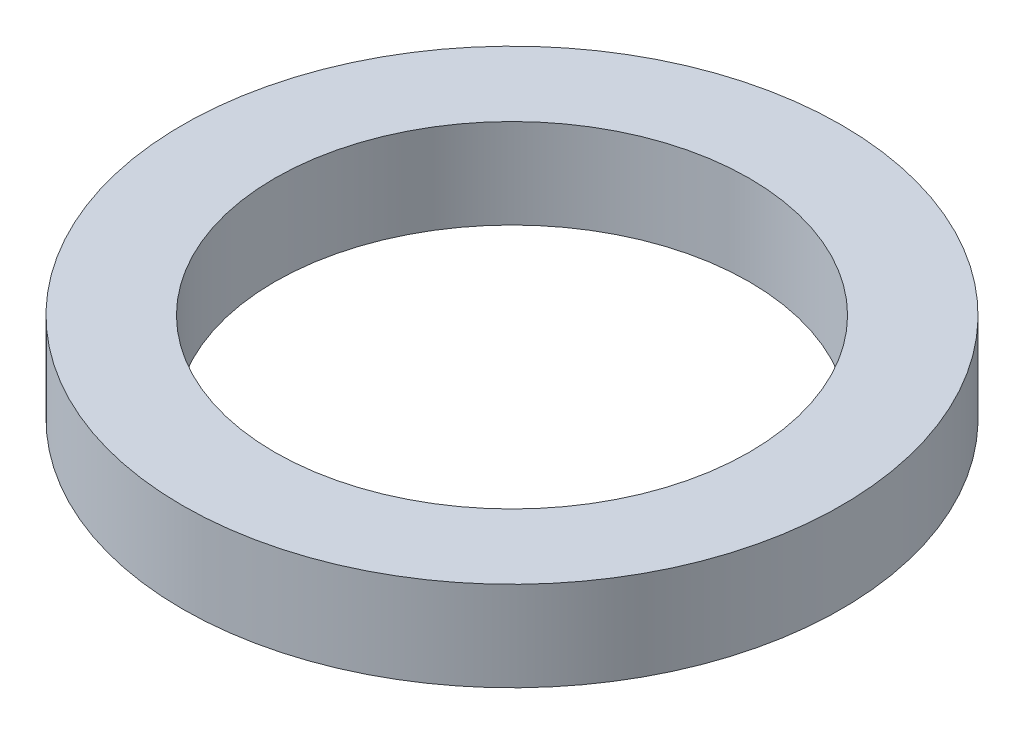
SolidWorks part; units mm, degrees
ref_plane "Front Plane" through (0, 0, 0) normal (0, 0, 1) x (1, 0, 0)
ref_plane "Top Plane" through (0, 0, 0) normal (0, 1, 0) x (1, 0, 0)
ref_plane "Right Plane" through (0, 0, 0) normal (1, 0, 0) x (0, 0, -1)
sketch "Sketch1" plane through (0, 0, 0) normal (0, 1, 0) x (1, 0, 0)
  circle A0 centre (0, 0) radius 62.5
  dimension "FLANGE_OD" = 125
extrude "Boss-Extrude1" add sketch "Sketch1" along normal blind 17
sketch "Sketch2" plane through (0, 0, 0) normal (0, 1, 0) x (1, 0, 0)
  circle A0 centre (0, 0) radius 45
  dimension "BORE_D" = 90
extrude "Cut-Extrude1" cut sketch "Sketch2" along normal through all
sketch "Sketch3" plane through (0, 17, 0) normal (0, 1, 0) x (1, 0, 0)
  circle A0 centre (0, 0) radius 27.1492 construction
  circle A1 centre (-27.1492, 0) radius 2.9057
  dimension "BOLT_D" = 5.8114
  dimension "BOLT_PCD" = 54.2983
extrude "Cut-Extrude2" cut sketch "Sketch3" against normal blind 16.1029 rebuild error yes
pattern_circular "CirPattern1" count 5 over 360 rebuild error yes
